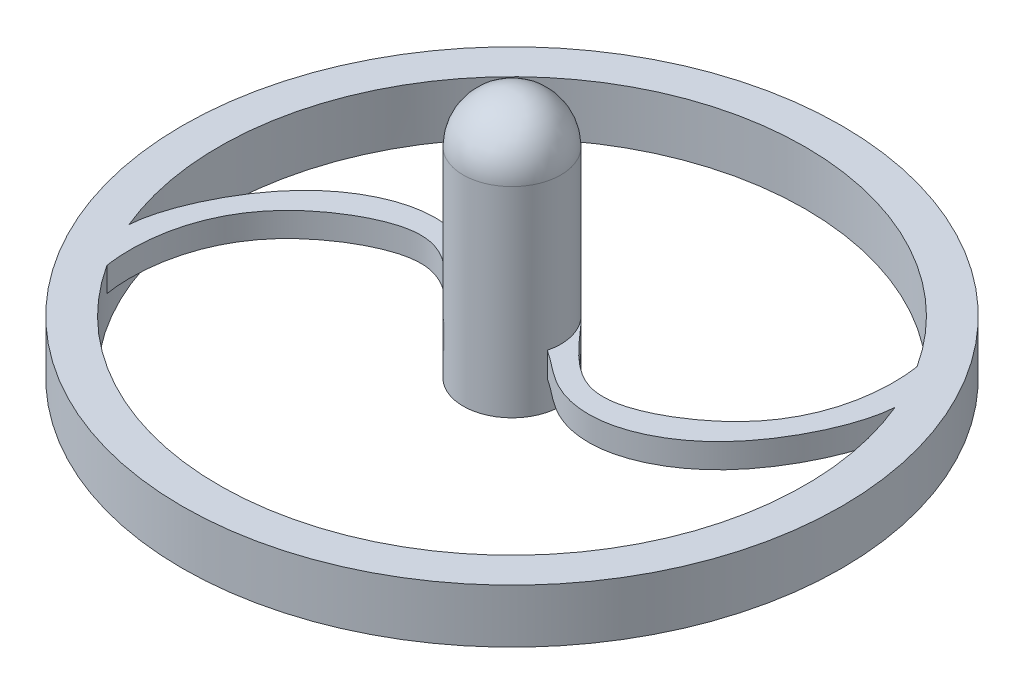
SolidWorks part; units mm, degrees
ref_plane "Alzado" through (0, 0, 0) normal (0, 0, 1) x (1, 0, 0)
ref_plane "Planta" through (0, 0, 0) normal (0, 1, 0) x (1, 0, 0)
ref_plane "Vista lateral" through (0, 0, 0) normal (1, 0, 0) x (0, 0, -1)
sketch "Croquis1" plane through (0, 0, 0) normal (0, 1, 0) x (1, 0, 0)
  line L0 (0, -16.6561) -> (0, 16.0593) construction
  line L1 (0, 13.5) -> (0, 12)
  line L4 (0, -12) -> (0, -13.5)
  line L5 (0, 2) -> (0, -2)
  arc A9 (0, 13.5) -> (0, -13.5) centre (0, 0) ccw
  arc A10 (0, 12) -> (-11.0823, -4.6025) centre (0, 0) ccw
  arc A11 (0, -12) -> (-10.0853, -6.5028) centre (0, 0) cw
  arc A12 (0, 2) -> (-1.9384, 0.4927) centre (0, 0) ccw
  arc A13 (0, -2) -> (-1.1626, -1.6274) centre (0, 0) cw
  spline S2 degree 3 poles (-10.0853, -6.5028) (-10.0828, -6.5066) (-10.9856, -2.0876) (-5.3663, 1.2923) (-2.9476, 0.6718) (-1.6606, -1.32) (-1.1626, -1.6274) knots 0 0 0 0 0.481215 0.664291 0.779226 1 1 1 1
  spline S3 degree 3 poles (-11.0823, -4.6025) (-11.0084, -3.3481) (-9.3196, 0.4597) (-5.8851, 2.1401) (-3.2565, 1.6835) (-2.522, 0.8529) (-1.9384, 0.4927) knots 0 0 0 0 0.307402 0.611772 0.741286 1 1 1 1
  point P12 (-9.0594, 0)
  point P15 (-8.4032, -0.9112)
  point P17 (-5.1616, 0.9655)
  point P19 (-3.4736, 0.612)
  point P20 (-11.0823, -4.6025)
  point P22 (-9.0086, 0)
  point P23 (-5.2539, 1.9117)
  point P24 (-9.022, -0.1327)
  point P25 (2.5358, 7.1726)
  point P29 (7.4761, 15.6958)
  dimension "D1" = 13.5
  dimension "D3" = 12
  dimension "D4" = 2
  dimension "D5" = 2
  dimension "D6" = 14.8472
  dimension "D7" = 13.0967
  dimension "D8" = 3.7697
  dimension "D9" = 0.0136
  dimension "D10" = 1.7558
  dimension "D11" = 2.0575
extrude "Saliente-Extruir1" add sketch "Croquis1" along normal blind 1
ref_axis "Eje1" through (0, 1.05, 0) along (0, -1, 0)
pattern_circular "MatrizC1" count 2 over 360 about axis through (0, 1.05, 0) along (0, -1, 0) of "Saliente-Extruir1"
sketch "Croquis2" plane through (0, 1, 0) normal (0, 1, 0) x (1, 0, 0)
  circle A0 centre (0, 0) radius 2
  arc A1 (-1.1626, -1.6274) -> (1.9384, -0.4927) centre (0, 0) ccw construction
extrude "Saliente-Extruir2" add sketch "Croquis2" along normal blind 8
fillet "Redondeo1" radius 2 1 edges at (0, 9, 2)
sketch "Croquis3" plane through (0, 0, 0) normal (0, -1, 0) x (1, 0, 0)
  circle A0 centre (0, 0) radius 13.5
  circle A1 centre (0, 0) radius 12
  circle A2 centre (0, 0) radius 13.5 construction
  arc A3 (11.0823, -4.6025) -> (-10.0853, 6.5028) centre (0, 0) ccw construction
extrude "Saliente-Extruir3" add sketch "Croquis3" along normal blind 1.2
sketch "Croquis4" plane through (0, 0, 0) normal (0, -1, 0) x (1, 0, 0)
  circle A0 centre (0, 0) radius 2
  arc A1 (1.9384, 0.4927) -> (-1.1626, 1.6274) centre (0, 0) ccw construction
extrude "Saliente-Extruir4" add sketch "Croquis4" along normal blind 1.2
